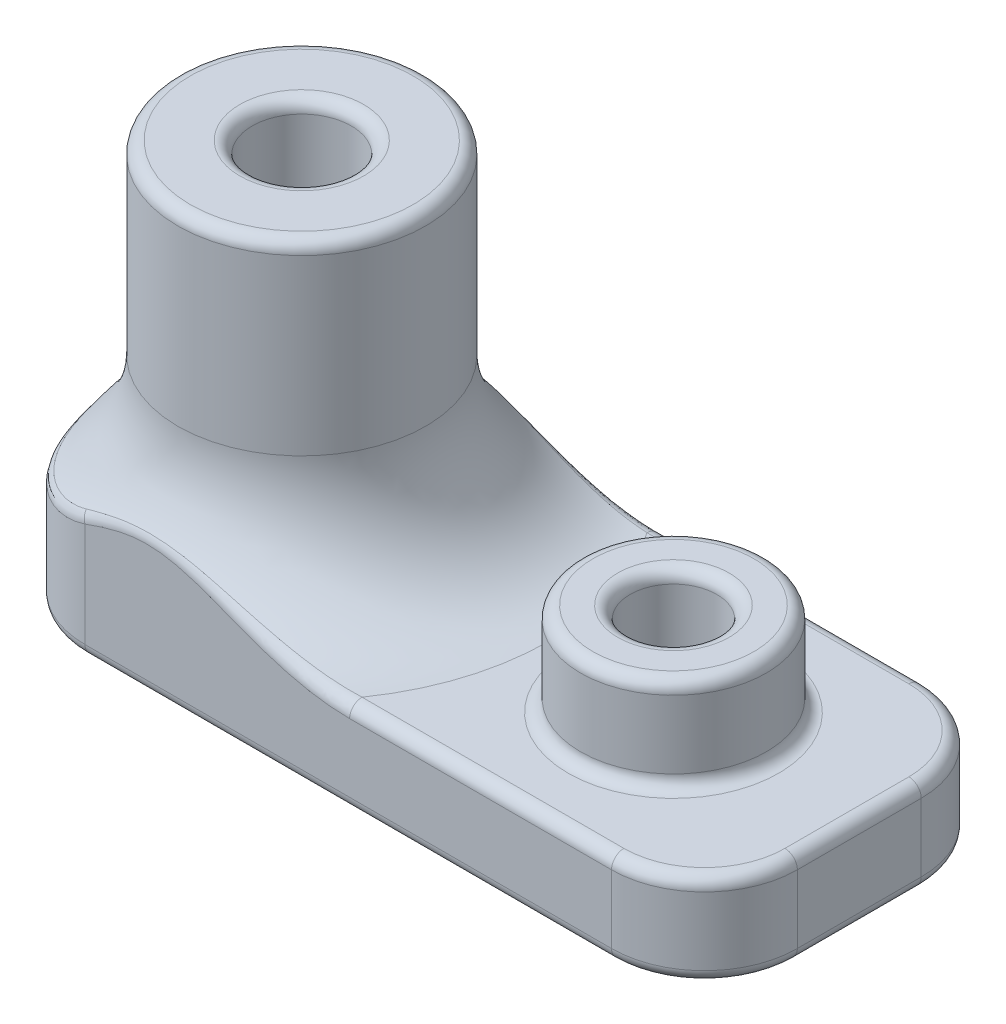
SolidWorks part; units mm, degrees
ref_plane "Front Plane" through (0, 0, 0) normal (0, 0, 1) x (1, 0, 0)
ref_plane "Top Plane" through (0, 0, 0) normal (0, 1, 0) x (1, 0, 0)
ref_plane "Right Plane" through (0, 0, 0) normal (1, 0, 0) x (0, 0, -1)
sketch "Sketch1" plane through (0, 0, 0) normal (0, 1, 0) x (1, 0, 0)
  line L1 (0, 0) -> (23, 0)
  line L2 (0, 0) -> (0, -10)
  line L3 (0, -10) -> (23, -10)
  line L4 (23, 0) -> (23, -10)
  dimension "D1" = 10
  dimension "D2" = 23
extrude "Boss-Extrude1" add sketch "Sketch1" along normal blind 3
sketch "Sketch2" plane through (0, 3, 0) normal (0, 1, 0) x (1, 0, 0)
  line L0 (23, 0) -> (0, 0) construction
  line L1 (0, 0) -> (0, -10) construction
  circle A0 centre (5, -5) radius 4
  dimension "D1" = 8
  dimension "D2" = 5
  dimension "D3" = 5
extrude "Boss-Extrude2" add sketch "Sketch2" along normal blind 10
sketch "Sketch3" plane through (0, 13, 0) normal (0, 1, 0) x (1, 0, 0)
  circle A0 centre (5, -5) radius 1.6
  dimension "D1" = 3.2
extrude "Cut-Extrude1" cut sketch "Sketch3" against normal through all
sketch "Sketch4" plane through (0, 3, 0) normal (0, 1, 0) x (1, 0, 0)
  line L5 (23, -10) -> (23, 0) construction
  circle A0 centre (17, -5) radius 1.4
  circle A1 centre (5, -5) radius 4 construction
  point P4 (23, -5)
  dimension "D1" = 0
  dimension "D3" = 2.8
  dimension "D2" = 12
extrude "Cut-Extrude2" cut sketch "Sketch4" against normal through all
sketch "Sketch5" plane through (0, 0, 0) normal (0, -1, 0) x (-1, 0, 0)
  circle A0 centre (-5, -5) radius 2.85
  dimension "D1" = 5.7
extrude "Cut-Extrude3" cut sketch "Sketch5" against normal blind 3
sketch "Sketch6" plane through (0, 3, 0) normal (0, 1, 0) x (1, 0, 0)
  circle A0 centre (17, -5) radius 1.4
  circle A1 centre (17, -5) radius 3
  dimension "D1" = 6
  dimension "D2" = 2.8
extrude "Boss-Extrude3" add sketch "Sketch6" along normal blind 3
fillet "Fillet1" radius 4 1 edges at (5, 3, 9)
fillet "Fillet3" radius 3 4 edges at (23, 1.5, 10) (23, 1.5, 0) (0, 1.5547, 10) (0, 1.5547, 0)
fillet "Fillet4" radius 0.4 21 edges at (8.5149, 3.4737, 10) (0.5799, 3.6519, 8.7729) (0, 4.3523, 5.1326) (1.2271, 3.6519, 0.5799) (4.8674, 4.3523, 0) (22.1213, 0, 0.8787) (11.5, 0, 0) (0.8787, 0, 0.8787) (0, 0, 5) (0.8787, 0, 9.1213) (11.5, 0, 10) (22.1213, 0, 9.1213) (23, 0, 5) (15.6225, 3, 0) (22.1213, 3, 0.8787) (23, 3, 5) (22.1213, 3, 9.1213) (15.6225, 3, 10) (5, 0, 2.15) (17, 0, 6.4) (17, 3, 8)
fillet "Fillet5" radius 0.4 4 edges at (5, 13, 9) (5, 13, 6.6) (17, 6, 6.4) (17, 6, 8)
